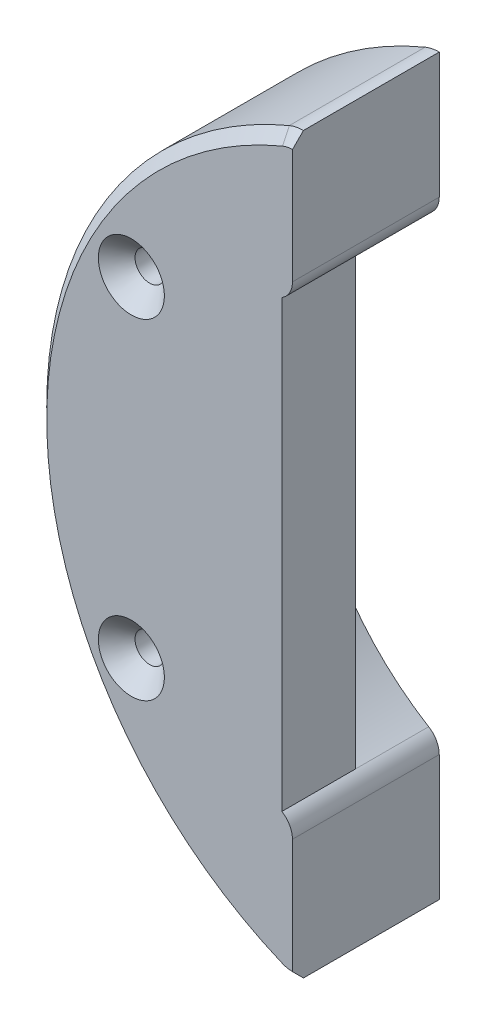
SolidWorks part; units mm, degrees
material "ABS"
ref_plane "前视基准面" through (0, 0, 0) normal (0, 0, 1) x (1, 0, 0)
ref_plane "上视基准面" through (0, 0, 0) normal (0, 1, 0) x (1, 0, 0)
ref_plane "右视基准面" through (0, 0, 0) normal (1, 0, 0) x (0, 0, -1)
sketch "草图1" plane through (0, 0, 0) normal (0, 0, 1) x (1, 0, 0)
  line L2 (-47, 33.0341) -> (-47, -33.0341) construction
  line L3 (-77.0235, 32.8833) -> (-77.0235, 50)
  line L4 (-77.0235, -32.8833) -> (-77.0235, -50)
  arc A4 (-78.4632, 30.3209) -> (-78.4632, -30.3209) centre (-60, 0) ccw
  arc A12 (-77.0235, 50) -> (-78.9499, 49.614) centre (-77.0235, 45) ccw
  arc A14 (-78.9499, 49.614) -> (-78.9499, -49.614) centre (-58.2353, 0) ccw
  arc A15 (-77.0235, -50) -> (-78.9499, -49.614) centre (-77.0235, -45) cw
  arc A16 (-78.4632, -30.3209) -> (-77.0235, -32.8833) centre (-80.0235, -32.8833) cw
  arc A17 (-78.4632, 30.3209) -> (-77.0235, 32.8833) centre (-80.0235, 32.8833) ccw
  circle A18 centre (-98.9711, 22.5) radius 2
  circle A19 centre (-98.9711, -22.5) radius 2
  point P33 (0, 0)
  point P34 (-62.4098, -35.4181)
  dimension "D1" = 35.5
  dimension "D2" = 3
  dimension "D3" = 4
  dimension "D4" = 4
extrude "凸台-拉伸1" add sketch "草图1" along normal mid plane 20 contours A4 A17 L3 A12 A14 A15 L4 A16 A19 A18 region at (-78.3317, 31.9327, 0)
chamfer "倒角1" distance 2.5 angle 45 2 edges at (-96.9711, -22.5, 10) (-96.9711, 22.5, 10)
chamfer "倒角2" distance 1.5 angle 45 3 edges at (-78.0058, 49.9025, 10) (-78.0058, -49.9025, 10) (-112, 0, 10)
ref_plane "基准面1" through (-78.372, 48.2298, 10) normal (-0.9228, -0.3853, 0) x (0, 0, 1)
sketch "草图4" plane through (0, 0, 0) normal (0, 0, 1) x (1, 0, 0)
  line L2 (-78.4632, -30.3209) -> (-78.4632, 30.3209)
  arc A0 (-78.4632, 30.3209) -> (-78.4632, -30.3209) centre (-60, 0) ccw
  arc A1 (-78.4632, 30.3209) -> (-78.4632, -30.3209) centre (-60, 0) ccw construction
extrude "凸台-拉伸2" add sketch "草图4" along normal blind 10
